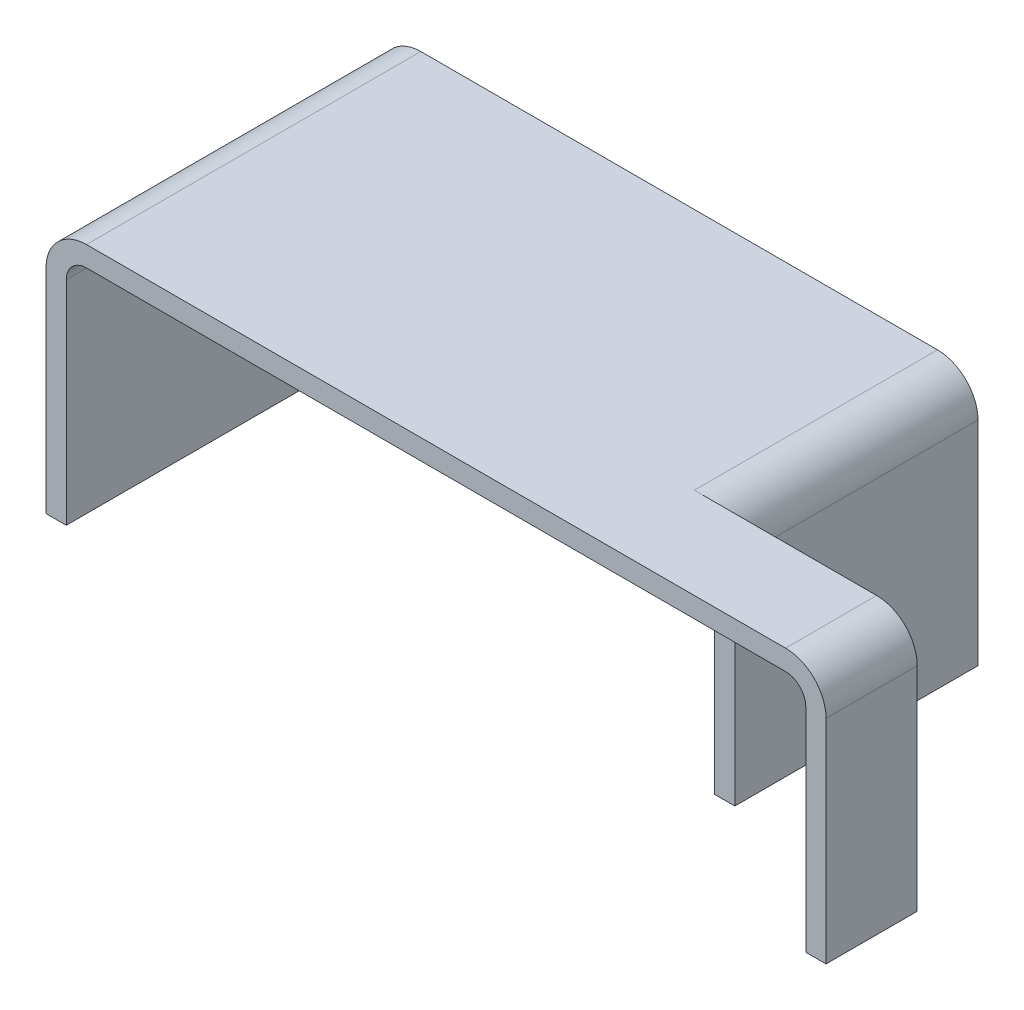
SolidWorks part; units mm, degrees
ref_plane "Front Plane" through (0, 0, 0) normal (0, 0, 1) x (1, 0, 0)
ref_plane "Top Plane" through (0, 0, 0) normal (0, 1, 0) x (1, 0, 0)
ref_plane "Right Plane" through (0, 0, 0) normal (1, 0, 0) x (0, 0, -1)
sketch "Sketch1" plane through (0, 0, 0) normal (0, 1, 0) x (1, 0, 0)
  line L11 (0, 0) -> (0, 33)
  line L12 (0, 33) -> (59, 33)
  line L13 (59, 33) -> (59, 9)
  line L14 (59, 9) -> (77, 9)
  line L15 (77, 9) -> (77, 0)
  line L16 (77, 0) -> (0, 0)
  dimension "D1" = 33
  dimension "D2" = 59
  dimension "D3" = 9
  dimension "D4" = 77
extrude "Boss-Extrude1" add sketch "Sketch1" along normal blind 25
sketch "Sketch3" plane through (0, 0, -33) normal (0, 0, -1) x (-1, 0, 0)
  line L8 (-59, 0) -> (0, 0) construction
  line L9 (-57, 0) -> (-2, 0)
  line L10 (-57, 0) -> (-57, 21)
  line L11 (-55, 23) -> (-4, 23)
  line L12 (-2, 0) -> (-2, 21)
  line L13 (-29.5, 23) -> (-29.5, 25) construction
  line L14 (-59, 25) -> (0, 25) construction
  line L15 (-59, 15.5043) -> (-57, 15.5043) construction
  line L16 (-59, 25) -> (-59, 0) construction
  arc A2 (-4, 23) -> (-2, 21) centre (-4, 21) cw
  arc A3 (-57, 21) -> (-55, 23) centre (-55, 21) cw
  dimension "D3" = 2
  dimension "D1" = 2
  dimension "D2" = 2
extrude "Cut-Extrude1" cut sketch "Sketch3" against normal through all
sketch "Sketch4" plane through (0, 0, 0) normal (0, 0, 1) x (1, 0, 0)
  line L7 (57, 0) -> (77, 0) construction
  line L8 (75, 0) -> (51.0803, 0)
  line L9 (75, 0) -> (75, 21)
  line L10 (73, 23) -> (51.0803, 23)
  line L11 (51.0803, 0) -> (51.0803, 23)
  line L12 (4, 23) -> (55, 23) construction
  line L13 (75, 18.3319) -> (77, 18.3319) construction
  line L14 (77, 25) -> (77, 0) construction
  arc A1 (75, 21) -> (73, 23) centre (73, 21) ccw
  dimension "D2" = 2
  dimension "D1" = 2
extrude "Cut-Extrude2" cut sketch "Sketch4" against normal up to vertex (9 mm away) up to point (59, 25, -9)
fillet "Fillet3" radius 4 3 edges at (0, 25, -16.5) (59, 25, -21) (77, 25, -4.5)
